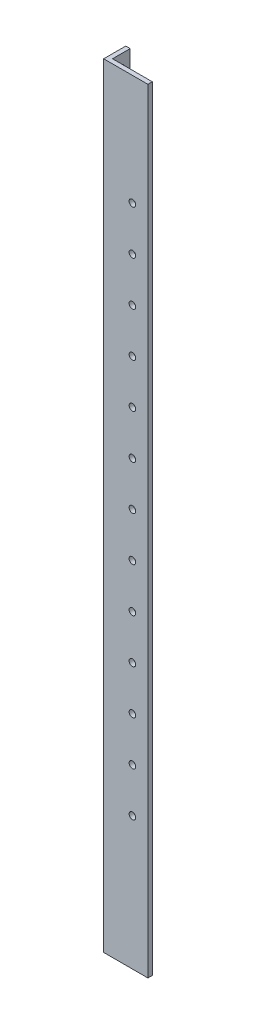
SolidWorks part; units mm, degrees
ref_plane "Front Plane" through (0, 0, 0) normal (0, 0, 1) x (1, 0, 0)
ref_plane "Top Plane" through (0, 0, 0) normal (0, 1, 0) x (1, 0, 0)
ref_plane "Right Plane" through (0, 0, 0) normal (1, 0, 0) x (0, 0, -1)
sketch "Sketch1" plane through (0, 0, 0) normal (0, 1, 0) x (1, 0, 0)
  line L0 (0, 0) -> (0, 10)
  line L1 (0, 10) -> (2, 10)
  line L2 (2, 10) -> (2, 2)
  line L3 (2, 2) -> (20, 2)
  line L4 (20, 2) -> (20, 0)
  line L5 (20, 0) -> (0, 0)
extrude "Boss-Extrude1" add sketch "Sketch1" along normal blind 350
hole_wizard "Ø3.0 (3) Diameter Hole1" positions "Sketch2" profile "Sketch3" hole size "Ø3.0" standard "ISO" end condition through all
sketch "Sketch2" plane through (2, 361.4076, -188.68) normal (1, 0, 0) x (0, 0, 1)
  point P0 (182.68, 355.4076)
  point P1 (182.68, 341.4076)
sketch "Sketch3" plane through (2, 6, -6) normal (0, 1, 0) x (0, 0, -1)
  line L0 (0, 0) -> (0, 2)
  line L1 (0, 2) -> (1.5, 2)
  line L2 (1.5, 2) -> (1.5, 0)
  line L3 (1.5, 0) -> (0, 0)
  line L4 (0, -6.35) -> (0, 107.95) construction
  dimension "Thru Hole Dia." = 3
  dimension "Thru Hole Depth" = 2
hole_wizard "Ø3.0 (3) Diameter Hole2" positions "Sketch4" profile "Sketch5" hole size "Ø3.0" standard "ISO" end condition through all
sketch "Sketch4" plane through (2, 361.4076, -188.68) normal (1, 0, 0) x (0, 0, 1)
  point P0 (182.68, 17.4076)
  point P1 (182.68, 31.4076)
sketch "Sketch5" plane through (2, 344, -6) normal (0, 1, 0) x (0, 0, -1)
  line L0 (0, 0) -> (0, 2)
  line L1 (0, 2) -> (1.5, 2)
  line L2 (1.5, 2) -> (1.5, 0)
  line L3 (1.5, 0) -> (0, 0)
  line L4 (0, -6.35) -> (0, 107.95) construction
  dimension "Thru Hole Dia." = 3
  dimension "Thru Hole Depth" = 2
sketch "Sketch6" plane through (0, 0, 0) normal (0, 0, 1) x (1, 0, 0)
  circle A0 centre (13, 300) radius 1.5
extrude "Cut-Extrude1" cut sketch "Sketch6" against normal through all
pattern_linear "LPattern1" count 13 spacing 20 along (0, -1, 0) of "Cut-Extrude1"
